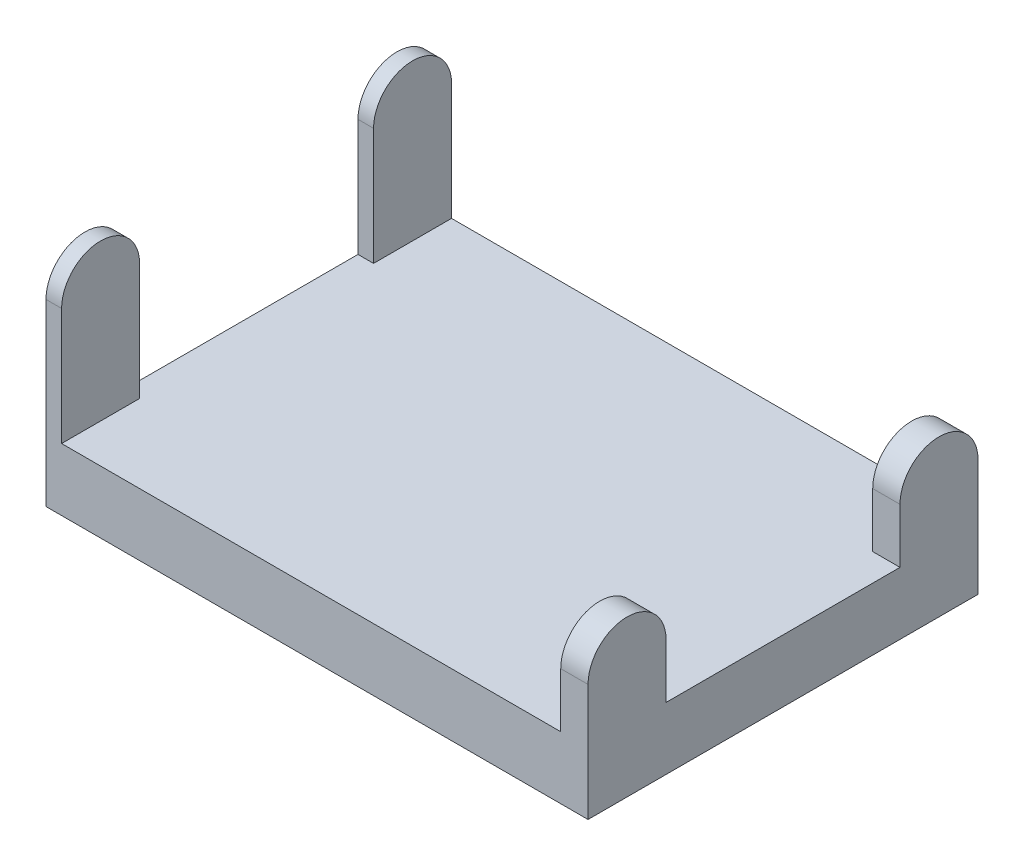
SolidWorks part; units mm, degrees
ref_plane "Front Plane" through (0, 0, 0) normal (0, 0, 1) x (1, 0, 0)
ref_plane "Top Plane" through (0, 0, 0) normal (0, 1, 0) x (1, 0, 0)
ref_plane "Right Plane" through (0, 0, 0) normal (1, 0, 0) x (0, 0, -1)
sketch "Sketch1" plane through (0, 0, 0) normal (0, 1, 0) x (1, 0, 0)
  line L1 (-17.375, 12.5) -> (17.375, 12.5)
  line L2 (-17.375, 12.5) -> (-17.375, -12.5)
  line L3 (-17.375, -12.5) -> (17.375, -12.5)
  line L4 (17.375, 12.5) -> (17.375, -12.5)
  line L5 (-17.375, 12.5) -> (17.375, -12.5) construction
  line L6 (-17.375, -12.5) -> (17.375, 12.5) construction
  point P0 (0, 0)
  dimension "D1" = 34.75
  dimension "D2" = 25
extrude "Boss-Extrude1" add sketch "Sketch1" along normal blind 4
sketch "Sketch2" plane through (0, 4, 0) normal (0, 1, 0) x (1, 0, 0)
  line L0 (0, 0) -> (-11.5388, 0) construction
  line L5 (0, 0) -> (0, -6.0099) construction
  line L10 (15.625, -12.5) -> (17.375, -12.5)
  line L11 (17.375, -7.5) -> (17.375, -12.5)
  line L12 (15.625, -7.5) -> (17.375, -7.5)
  line L13 (15.625, -7.5) -> (15.625, -12.5)
  line L14 (15.625, 7.5) -> (15.625, 12.5)
  line L15 (15.625, 7.5) -> (17.375, 7.5)
  line L16 (17.375, 7.5) -> (17.375, 12.5)
  line L17 (15.625, 12.5) -> (17.375, 12.5)
extrude "Boss-Extrude2" add sketch "Sketch2" along normal blind 6
sketch "Sketch4" plane through (0, 4, 0) normal (0, 1, 0) x (1, 0, 0)
  line L0 (0, 0) -> (-3.5816, 0) construction
  line L1 (-17.375, 12.5) -> (-16.375, 12.5)
  line L2 (-17.375, 12.5) -> (-17.375, 7.5)
  line L3 (-17.375, 7.5) -> (-16.375, 7.5)
  line L4 (-16.375, 12.5) -> (-16.375, 7.5)
  line L5 (-17.375, -7.5) -> (-16.375, -7.5)
  line L6 (-16.375, -12.5) -> (-16.375, -7.5)
  line L7 (-17.375, -12.5) -> (-16.375, -12.5)
  line L8 (-17.375, -12.5) -> (-17.375, -7.5)
  dimension "D1" = 5
  dimension "D2" = 1
extrude "Boss-Extrude3" add sketch "Sketch4" along normal blind 10
fillet "Fillet2" 2 edges at (-16.875, 14, -12.5) (-16.875, 14, -7.5) type full round first side face at (-0.1875, 7, -12.5) second side face at (-16.875, 9, -7.5) middle face at (-16.875, 14, -10)
fillet "Fillet3" 2 edges at (-16.875, 14, 7.5) (-16.875, 14, 12.5) type full round first side face at (-16.875, 9, 7.5) second side face at (-0.1875, 7, 12.5) middle face at (-16.875, 14, 10)
fillet "Fillet4" 2 edges at (16.5, 10, -7.5) (16.5, 10, -12.5) type full round first side face at (16.5, 7, -7.5) second side face at (-0.1875, 6.375, -12.5) middle face at (16.5, 10, -10)
fillet "Fillet5" 2 edges at (16.5, 10, 12.5) (16.5, 10, 7.5) type full round first side face at (-0.1875, 6.375, 12.5) second side face at (16.5, 7, 7.5) middle face at (16.5, 10, 10)
